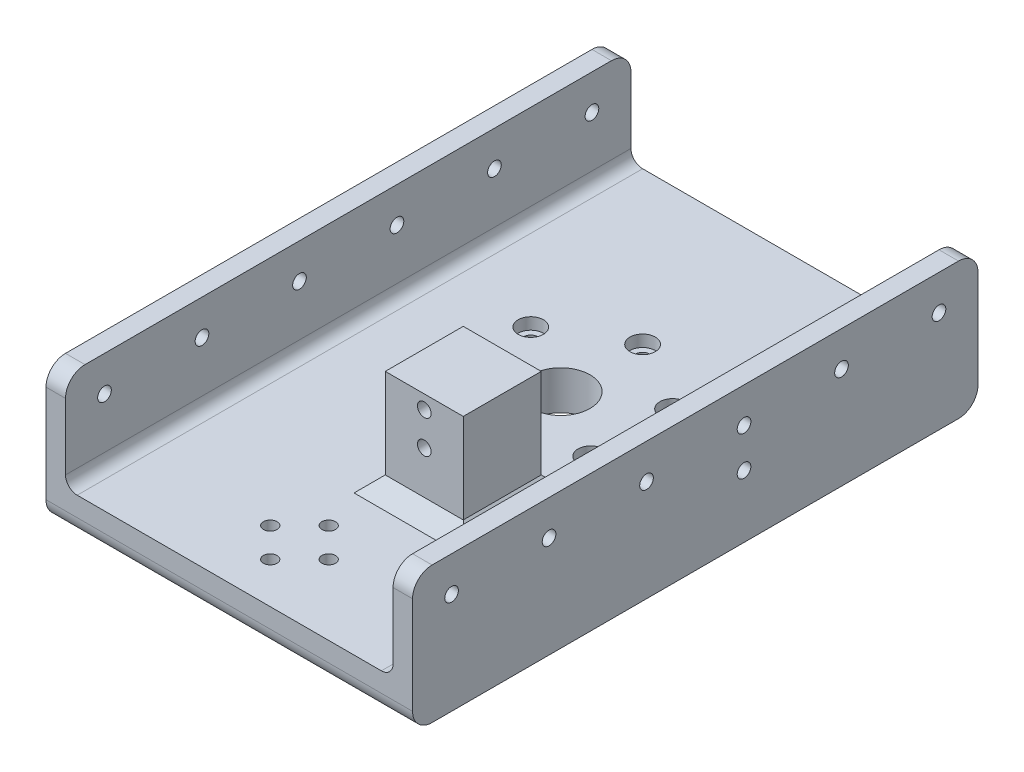
SolidWorks part; units mm, degrees
ref_plane "Front Plane" through (0, 0, 0) normal (0, 0, 1) x (1, 0, 0)
ref_plane "Top Plane" through (0, 0, 0) normal (0, 1, 0) x (1, 0, 0)
ref_plane "Right Plane" through (0, 0, 0) normal (1, 0, 0) x (0, 0, -1)
sketch "Sketch1" plane through (0, 0, 0) normal (0, 0, 1) x (1, 0, 0)
  line L0 (0, 0) -> (0, 35) construction
  line L1 (-47, 35) -> (-47, 0)
  line L2 (-47, 0) -> (47, 0)
  line L3 (-47, 35) -> (-42, 35)
  line L4 (-42, 35) -> (-42, 10)
  line L5 (-42, 10) -> (42, 10)
  line L6 (42, 35) -> (42, 10)
  line L7 (47, 35) -> (42, 35)
  line L8 (47, 35) -> (47, 0)
  point P9 (0, 10)
  dimension "D1" = 35
  dimension "D2" = 5
  dimension "D3" = 10
  dimension "D4" = 42
extrude "Boss-Extrude1" add sketch "Sketch1" along normal blind 85 and the other way blind 60
sketch "Sketch4" plane through (0, 10, 0) normal (0, 1, 0) x (1, 0, 0)
  circle A0 centre (0, 0) radius 7.5
  dimension "D1" = 15
extrude "Cut-Extrude1" cut sketch "Sketch4" against normal blind 80
sketch "Sketch2" plane through (0, 10, 0) normal (0, 1, 0) x (1, 0, 0)
  circle A0 centre (0, 0) radius 21 construction
  circle A1 centre (0, 21) radius 1.75
  point P3 (0, 21)
  dimension "D1" = 3.5
  dimension "42" = 42
hole_wizard "CBORE for M3 SHCS1" positions "Sketch2" profile "Sketch3" counterbore size "M3" standard "ANSI Metric" end condition through all
sketch "Sketch3" plane through (0, 10, -21) normal (1, 0, 0) x (0, 0, 1)
  line L0 (0, 0) -> (0, 10)
  line L1 (0, 10) -> (1.75, 10)
  line L3 (1.75, 10) -> (1.75, 3)
  line L4 (1.75, 3) -> (3.25, 3)
  line L5 (3.25, 3) -> (3.25, 0)
  line L7 (3.25, 0) -> (0, 0)
  line L11 (0, -6.35) -> (0, 107.95) construction
  dimension "Thru Hole Dia." = 3.5
  dimension "Thru Hole Depth" = 10
  dimension "C'Bore Dia." = 6.5
  dimension "C'Bore Depth" = 3
pattern_circular "CirPattern1" count 6 over 360 about axis through (0, -70, 0) along (0, 1, 0) of "CBORE for M3 SHCS1" reverse direction yes
sketch "Sketch5" plane through (-47, 0, 0) normal (-1, 0, 0) x (0, 0, 1)
  line L0 (-60, 35) -> (-60, 0) construction
  circle A0 centre (-50, 26) radius 1.75
  dimension "D1" = 10
  dimension "D2" = 3.5
  dimension "D3" = 16
extrude "Cut-Extrude2" cut sketch "Sketch5" against normal through all
pattern_linear "LPattern1" count 6 spacing 25 along (0, 0, 1) of "Cut-Extrude2"
sketch "Sketch6" plane through (0, 10, 0) normal (0, 1, 0) x (1, 0, 0)
  circle A0 centre (0, -67) radius 7.5 construction
  circle A1 centre (0, -59.5) radius 1.75
  circle A2 centre (7.5, -67) radius 1.75
  circle A3 centre (0, -74.5) radius 1.75
  circle A4 centre (-7.5, -67) radius 1.75
  dimension "D1" = 67
  dimension "D2" = 15
  dimension "D3" = 3.5
  dimension "D4" = 4
extrude "Cut-Extrude3" cut sketch "Sketch6" against normal through all
fillet "Fillet1" radius 5 6 edges at (0, 0, 85) (0, 0, -60) (44.5, 35, -60) (44.5, 35, 85) (-44.5, 35, 85) (-44.5, 35, -60)
fillet "Fillet2" radius 3 2 edges at (42, 10, 12.5) (-42, 10, 12.5)
sketch "Sketch9" plane through (47, 0, 0) normal (1, 0, 0) x (0, 0, -1)
  circle A0 centre (0, 16) radius 1.75
  point P3 (0, 26)
  dimension "D1" = 3.5
  dimension "D2" = 10
extrude "Cut-Extrude6" cut sketch "Sketch9" against normal blind 10
sketch "Sketch10" plane through (42, 0, 0) normal (-1, 0, 0) x (0, 0, 1)
  circle A0 centre (0, 16) radius 3
  dimension "D1" = 6
extrude "Cut-Extrude7" cut sketch "Sketch10" against normal blind 1.5
sketch "Sketch11" plane through (0, 10, 0) normal (0, 1, 0) x (1, 0, 0)
  line L1 (0, -45) -> (20, -45)
  line L2 (0, -45) -> (0, -25)
  line L3 (0, -25) -> (20, -25)
  line L4 (20, -45) -> (20, -25)
  line L5 (0, -45) -> (20, -25) construction
  line L6 (0, -25) -> (20, -45) construction
  circle A0 centre (10, -35) radius 10
  circle M9 centre (0, -21) radius 3.25
  dimension "D1" = 20
  dimension "D3" = 32
  dimension "D2" = 10
extrude "Boss-Extrude2" add sketch "Sketch11" along normal blind 27 contours A0 L4 L3 | A0 L1 L4 | A0 | A0 L3 L2 M9 | A0 L2 L1 region at (2.2337, 10, 42.7663) region at (17.7663, 10, 42.7663) region at (10, 10, 35) region at (2.2337, 10, 27.2337) region at (17.7663, 10, 27.2337)
sketch "Sketch12" plane through (0, 0, 0) normal (0, 0, 1) x (1, 0, 0)
  line L0 (0, 37) -> (20, 37) construction
  line L1 (39, 10) -> (-39, 10) construction
  circle A0 centre (10, 25) radius 1.75
  circle A1 centre (10, 33.5) radius 1.75
  point P6 (0, 0)
  point P7 (0, 0)
  point P9 (0, 0)
  point P11 (10, 37)
  dimension "D1" = 3.5
  dimension "D2" = 3.5
  dimension "D3" = 15
  dimension "D4" = 23.5
extrude "Cut-Extrude8" cut sketch "Sketch12" along normal through all
chamfer "Chamfer1" distance 4 angle 45 4 edges at (10, 10, 25) (20, 10, 35) (0, 10, 35) (10, 10, 45)
